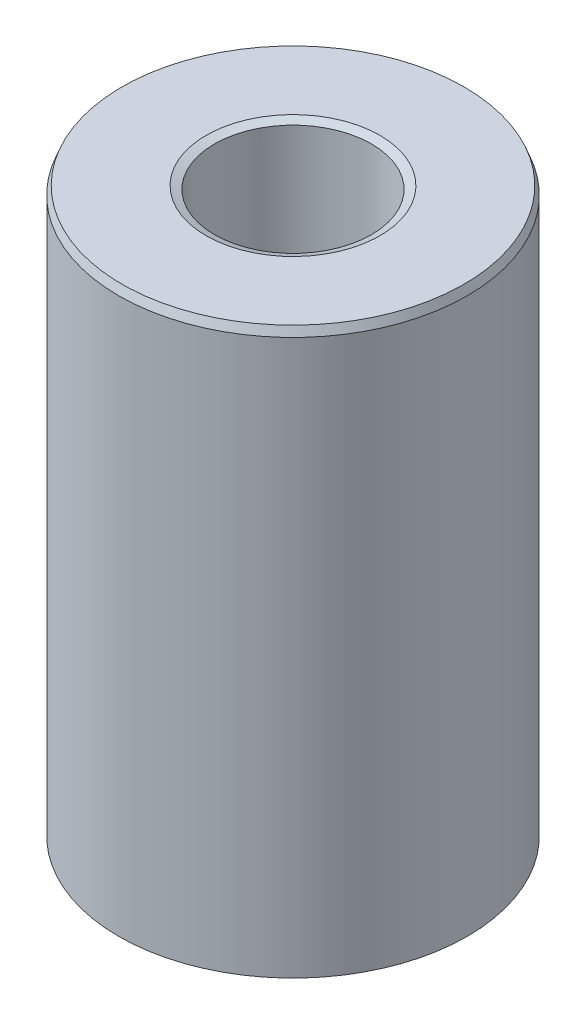
SolidWorks part; units mm, degrees
ref_plane "Front Plane" through (0, 0, 0) normal (0, 0, 1) x (1, 0, 0)
ref_plane "Top Plane" through (0, 0, 0) normal (0, 1, 0) x (1, 0, 0)
ref_plane "Right Plane" through (0, 0, 0) normal (1, 0, 0) x (0, 0, -1)
sketch "Sketch1" plane through (0, 0, 0) normal (0, 1, 0) x (1, 0, 0)
  circle A0 centre (0, 0) radius 40
  dimension "SLEEVE_OD" = 80
extrude "Boss-Extrude1" add sketch "Sketch1" along normal blind 130.0474
sketch "Sketch2" plane through (0, 0, 0) normal (0, 1, 0) x (1, 0, 0)
  circle A0 centre (0, 0) radius 18.0379
  dimension "BORE_D" = 36.0758
extrude "Cut-Extrude1" cut sketch "Sketch2" along normal through all
chamfer "Chamfer1" distance 1.9233 angle 21.064 4 edges at (0, 130.0474, 18.0379) (0, 0, 18.0379) (0, 0, 40) (0, 130.0474, 40) first distance on face at (0, 130.0474, 18.0379) first distance on face at (0, 0, 18.0379) first distance on face at (0, 130.0474, 40)
